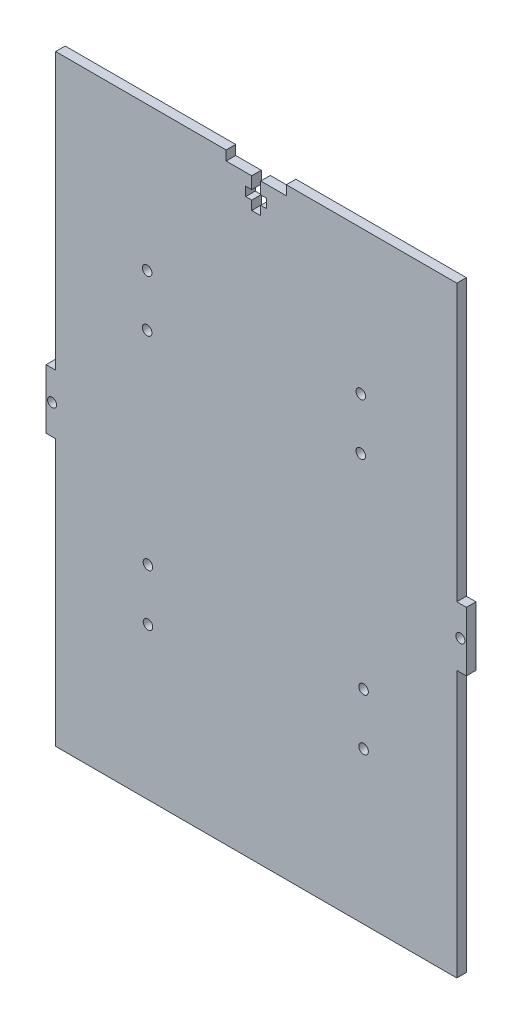
SolidWorks part; units mm, degrees
ref_plane "Front Plane" through (0, 0, 0) normal (0, 0, 1) x (1, 0, 0)
ref_plane "Top Plane" through (0, 0, 0) normal (0, 1, 0) x (1, 0, 0)
ref_plane "Right Plane" through (0, 0, 0) normal (1, 0, 0) x (0, 0, -1)
sketch "Sketch1" plane through (0, 0, 0) normal (0, 0, 1) x (1, 0, 0)
  line L1 (-69.85, 101.6) -> (69.85, 101.6)
  line L2 (-69.85, 101.6) -> (-69.85, -101.6)
  line L3 (-69.85, -101.6) -> (69.85, -101.6)
  line L4 (69.85, 101.6) -> (69.85, -101.6)
  line L5 (-69.85, 101.6) -> (69.85, -101.6) construction
  line L6 (-69.85, -101.6) -> (69.85, 101.6) construction
  point P0 (0, 0)
  dimension "D1" = 203.2
  dimension "D2" = 139.7
extrude "Boss-Extrude1" add sketch "Sketch1" along normal blind 3.18
sketch "Sketch2" plane through (0, 0, 3.18) normal (0, 0, 1) x (1, 0, 0)
  line L0 (0, 0) -> (69.85, 0) construction
  line L1 (-10, 101.6) -> (10, 101.6)
  line L2 (-10, 101.6) -> (-10, 98.42)
  line L3 (-10, 98.42) -> (-1.5, 98.42)
  line L4 (10, 101.6) -> (10, 98.42)
  line L5 (69.85, -101.6) -> (69.85, 101.6) construction
  line L6 (0, 0) -> (0, 101.6) construction
  line L7 (-1.5, 88.42) -> (1.5, 88.42)
  line L8 (-1.5, 88.42) -> (-1.5, 91.42)
  line L10 (1.5, 88.42) -> (1.5, 91.42)
  line L12 (69.85, 101.6) -> (-69.85, 101.6) construction
  line L13 (3.5, 94.42) -> (1.5, 94.42)
  line L14 (3.5, 94.42) -> (3.5, 91.42)
  line L15 (3.5, 91.42) -> (1.5, 91.42)
  line L16 (-3.5, 94.42) -> (-3.5, 91.42)
  line L17 (-10, -101.6) -> (-10, -98.42)
  line L18 (-10, -98.42) -> (-1.5, -98.42)
  line L19 (-1.5, -94.42) -> (-1.5, -98.42)
  line L20 (-1.5, -94.42) -> (-3.5, -94.42)
  line L21 (-3.5, -94.42) -> (-3.5, -91.42)
  line L22 (1.5, 98.42) -> (10, 98.42)
  line L23 (-1.5, 94.42) -> (-3.5, 94.42)
  line L24 (-1.5, -91.42) -> (-3.5, -91.42)
  line L25 (-1.5, -88.42) -> (-1.5, -91.42)
  line L26 (-1.5, -88.42) -> (1.5, -88.42)
  line L27 (-1.5, 91.42) -> (-3.5, 91.42)
  line L28 (1.5, -88.42) -> (1.5, -91.42)
  line L29 (-1.5, 94.42) -> (-1.5, 98.42)
  line L30 (1.5, 94.42) -> (1.5, 98.42)
  line L31 (3.5, -91.42) -> (1.5, -91.42)
  line L32 (3.5, -94.42) -> (3.5, -91.42)
  line L33 (3.5, -94.42) -> (1.5, -94.42)
  line L34 (1.5, -94.42) -> (1.5, -98.42)
  line L35 (1.5, -98.42) -> (10, -98.42)
  line L36 (10, -101.6) -> (10, -98.42)
  line L37 (-10, -101.6) -> (10, -101.6)
  line L38 (-69.85, 101.6) -> (-69.85, -101.6) construction
  line L39 (-69.85, 101.6) -> (-66.67, 101.6)
  line L40 (-69.85, 101.6) -> (-69.85, 9.875)
  line L41 (-69.85, 9.875) -> (-66.67, 9.875)
  line L42 (-66.67, 101.6) -> (-66.67, 9.875)
  line L43 (-69.85, -101.6) -> (-66.67, -101.6)
  line L44 (-69.85, -101.6) -> (-69.85, -9.875)
  line L45 (-69.85, -9.875) -> (-66.67, -9.875)
  line L46 (-66.67, -101.6) -> (-66.67, -9.875)
  line L47 (69.85, -9.875) -> (66.67, -9.875)
  line L48 (66.67, -101.6) -> (66.67, -9.875)
  line L49 (69.85, -101.6) -> (66.67, -101.6)
  line L50 (69.85, -101.6) -> (69.85, -9.875)
  line L51 (69.85, 9.875) -> (66.67, 9.875)
  line L52 (66.67, 101.6) -> (66.67, 9.875)
  line L53 (69.85, 101.6) -> (66.67, 101.6)
  line L54 (69.85, 101.6) -> (69.85, 9.875)
  circle A0 centre (-67.85, 0) radius 1.5
  circle A1 centre (67.85, 0) radius 1.5
  point P0 (0, 50.5662)
  point P5 (0, 32.0079)
  point P10 (15.4931, 34.4893)
  dimension "D11" = 3
  dimension "D12" = 2
  dimension "D1" = 20
  dimension "D2" = 19.75
  dimension "D3" = 4
  dimension "D4" = 3
  dimension "D5" = 3.18
  dimension "D6" = 7
  dimension "D7" = 3
  dimension "D8" = 3
  dimension "D9" = 3.18
  dimension "D10" = 3.18
extrude "Cut-Extrude1" cut sketch "Sketch2" against normal through all
sketch "Sketch3" plane through (0, 0, 0) normal (0, 0, -1) x (-1, 0, 0)
  circle A0 centre (-35.6713, -47.9634) radius 1.59
  circle A1 centre (-35.6713, -30.7773) radius 1.59
extrude "Cut-Extrude2" cut sketch "Sketch3" against normal through all
sketch "Sketch4" plane through (0, 0, 0) normal (0, 0, -1) x (-1, 0, 0)
  circle A0 centre (-34.7507, 53.7803) radius 1.59
  circle A1 centre (-34.7507, 36.5942) radius 1.59
  circle A2 centre (36.2498, 53.7803) radius 1.59
  circle A3 centre (36.2498, 36.5942) radius 1.59
  circle A4 centre (35.9839, -30.7773) radius 1.59
  circle A5 centre (35.9839, -47.9634) radius 1.59
  circle A6 centre (-35.6713, -30.7773) radius 1.59
  circle A7 centre (-35.6713, -47.9634) radius 1.59
extrude "Cut-Extrude3" cut sketch "Sketch4" against normal through all
sketch "Sketch5" plane through (-66.67, 0, 0) normal (-1, 0, 0) x (0, 0, 1)
  line L1 (3.18, -98.42) -> (0, -98.42)
  line L2 (3.18, -98.42) -> (3.18, -101.6)
  line L3 (3.18, -101.6) -> (0, -101.6)
  line L4 (0, -98.42) -> (0, -101.6)
extrude "Cut-Extrude4" cut sketch "Sketch5" against normal through all
sketch "Sketch6" plane through (0, 0, 0) normal (0, 0, -1) x (-1, 0, 0)
  line L0 (1.5, -98.42) -> (66.67, -98.42) construction
  line L1 (15.2765, -98.42) -> (-16.9255, -98.42)
  line L2 (15.2765, -98.42) -> (15.2765, -83.4521)
  line L3 (15.2765, -83.4521) -> (-16.9255, -83.4521)
  line L4 (-16.9255, -98.42) -> (-16.9255, -83.4521)
extrude "Boss-Extrude4" add sketch "Sketch6" against normal through all
